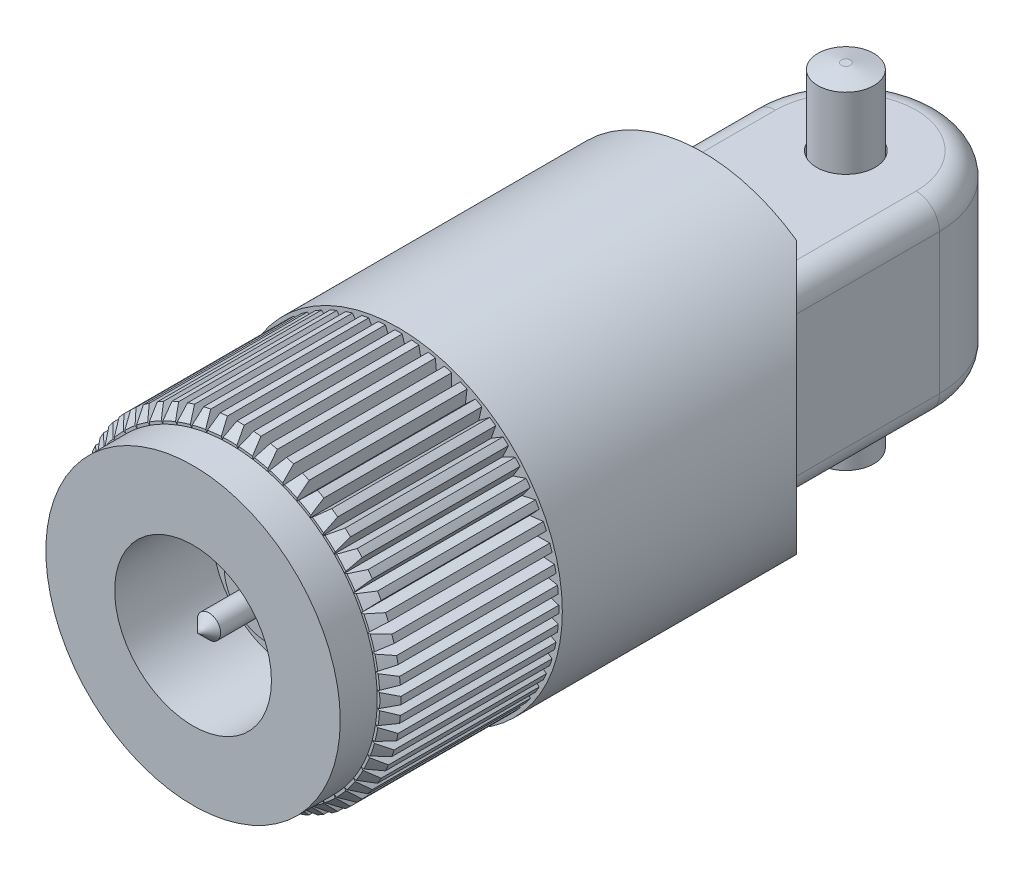
SolidWorks part; units mm, degrees
ref_plane "Front Plane" through (0, 0, 0) normal (0, 0, 1) x (1, 0, 0)
ref_plane "Top Plane" through (0, 0, 0) normal (0, 1, 0) x (1, 0, 0)
ref_plane "Right Plane" through (0, 0, 0) normal (1, 0, 0) x (0, 0, -1)
sketch "Sketch1" plane through (0, 0, 0) normal (0, 0, 1) x (1, 0, 0)
  circle A0 centre (0, 0) radius 7
  dimension "D1" = 14
extrude "Boss-Extrude1" add sketch "Sketch1" along normal blind 13
sketch "Sketch2" plane through (0, 0, 0) normal (0, 1, 0) x (1, 0, 0)
  line L0 (4, 0) -> (7, -3)
  line L1 (7, -3) -> (7, 0)
  line L2 (7, 0) -> (4, 0)
  line L3 (0, 0) -> (7, 0) construction
  line L4 (7, 0) -> (-7, 0) construction
  line L5 (7, -13) -> (7, 0) construction
  dimension "D1" = 45
  dimension "D2" = 3
extrude "Cut-Extrude1" cut sketch "Sketch2" against normal blind 13 and the other way blind 13
sketch "Sketch3" plane through (0, 0, 0) normal (0, 1, 0) x (1, 0, 0)
  line L0 (4, 0) -> (4, 6.116)
  line L1 (4, 6.116) -> (-4, 6.116) construction
  line L2 (-4, 6.116) -> (-4, 0)
  line L3 (4, 0) -> (-7, 0) construction
  line L4 (-4, 0) -> (4, 0)
  arc A0 (4, 6.116) -> (-4, 6.116) centre (0, 6.116) ccw
  circle A1 centre (0, 6.116) radius 1.25
  point P8 (0, 0)
  dimension "D1" = 2.5
extrude "Boss-Extrude2" add sketch "Sketch3" along normal blind 4 and the other way blind 4
sketch "Sketch4" plane through (0, 0, 13) normal (0, 0, 1) x (1, 0, 0)
  circle A0 centre (0, 0) radius 6.85
  dimension "D1" = 13.7
extrude "Boss-Extrude3" add sketch "Sketch4" along normal blind 7.2
sketch "Sketch5" plane through (0, 0, 20.2) normal (0, 0, 1) x (1, 0, 0)
  circle A0 centre (0, 0) radius 6.29
  dimension "D1" = 12.58
extrude "Boss-Extrude4" add sketch "Sketch5" along normal blind 1.58
chamfer "Chamfer1" distance 0.45 angle 45 1 edges at (6.85, 0, 20.2)
sketch "Sketch6" plane through (0, 0, 13) normal (0, 0, 1) x (1, 0, 0)
  line L0 (0, 0) -> (0, 8.2464) construction
  line L1 (0, 6.85) -> (0.1553, 6.85)
  line L2 (1.0138, 9.6453) -> (0, 0) construction
  line L3 (0.1553, 6.85) -> (0.3292, 6.2814)
  line L4 (0.3292, 6.2814) -> (0.5615, 6.8287)
  line L5 (0.5615, 6.8287) -> (0.716, 6.8125)
  line L6 (0, 6.85) -> (0.3292, 6.2814) construction
  line L7 (0.716, 6.8125) -> (0.3292, 6.2814) construction
  line L8 (0, 6.85) -> (0.716, 6.8125) construction
  line L9 (0.358, 6.8312) -> (0.3292, 6.2814) construction
  line L10 (0.1553, 6.85) -> (0.5615, 6.8287) construction
  line L11 (0, 6.85) -> (0, 7.3361)
  line L12 (0, 7.3361) -> (0.7668, 7.2959)
  line L13 (0.7668, 7.2959) -> (0.716, 6.8125)
  circle A0 centre (0, 0) radius 6.85 construction
  circle A1 centre (0, 0) radius 6.29 construction
  circle A2 centre (0, 0) radius 6.85 construction
  point P16 (0.3584, 6.8394)
  dimension "D1" = 6
  dimension "D2" = 40
extrude "Cut-Extrude2" cut sketch "Sketch6" along normal up to surface (7.2 mm away) up to face at (6.4, 0, 20.2)
pattern_circular "CirPattern1" count 60 over 360 about axis through (0, 0, 20.2) along (0, 0, -1) of "Cut-Extrude2"
fillet "Fillet1" radius 1 6 edges at (-4, -4, -3.058) (-4, 4, -3.058) (0, 4, -10.116) (0, -4, -10.116)
sketch "Sketch7" plane through (0, 0, 21.78) normal (0, 0, 1) x (1, 0, 0)
  circle A0 centre (0, 0) radius 3.35
  dimension "D1" = 6.7
extrude "Cut-Extrude3" cut sketch "Sketch7" against normal blind 4.18
sketch "Sketch8" plane through (0, 0, 17.6) normal (0, 0, 1) x (1, 0, 0)
  circle A0 centre (0, 0) radius 1.85
  dimension "D1" = 3.7
extrude "Boss-Extrude5" add sketch "Sketch8" along normal blind 1
sketch "Sketch9" plane through (0, 0, 18.6) normal (0, 0, 1) x (1, 0, 0)
  circle A0 centre (0, 0) radius 0.5
  dimension "D1" = 1
extrude "Boss-Extrude6" add sketch "Sketch9" along normal blind 3
chamfer "Chamfer2" distance 0.5 angle 45 1 edges at (0.5, 0, 21.6)
sketch "Sketch10" plane through (0, 0, 0) normal (0, 1, 0) x (1, 0, 0)
  circle A0 centre (0, 6.116) radius 1.1944
extrude "Boss-Extrude7" add sketch "Sketch10" along normal blind 7.25 and the other way blind 7.25 separate body
chamfer "Chamfer3" distance 0.25 distance2 1 1 edges at (0, 7.25, -4.9216) first distance on face at (0, -7.25, -4.9216)
chamfer "Chamfer4" distance 1 distance2 0.25 1 edges at (0, -7.25, -4.9216) first distance on face at (0, -7.25, -4.9216)
